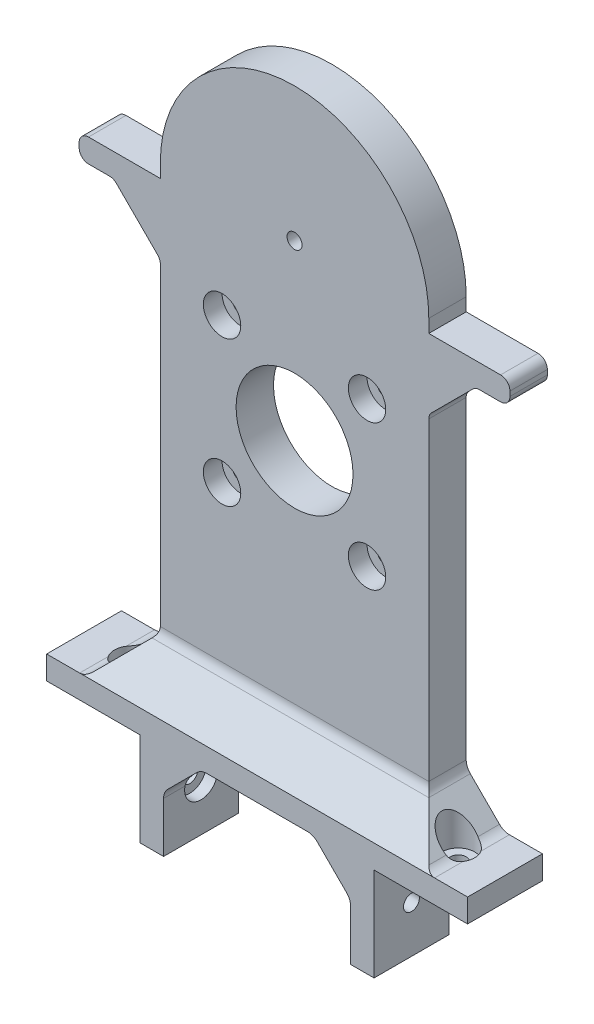
SolidWorks part; units mm, degrees
ref_plane "Plano frontal" through (0, 0, 0) normal (0, 0, 1) x (1, 0, 0)
ref_plane "Plano superior" through (0, 0, 0) normal (0, 1, 0) x (1, 0, 0)
ref_plane "Plano direito" through (0, 0, 0) normal (1, 0, 0) x (0, 0, -1)
sketch "Esboço1" plane through (0, 0, 0) normal (0, 0, 1) x (1, 0, 0)
  line L0 (-20, 0) -> (20, 0)
  line L1 (-20, 0) -> (-20, -20)
  line L2 (-20, -20) -> (-25, -20)
  line L3 (-25, -20) -> (-25, 0)
  line L4 (-25, 0) -> (-45, 0)
  line L5 (-45, 0) -> (-45, 5)
  line L6 (-45, 5) -> (-28.7, 5)
  line L7 (-28.7, 5) -> (-28.7, 100)
  line L8 (0, -20) -> (0, 100) construction
  line L9 (-28.7, 100) -> (28.7, 100) construction
  line L10 (28.7, 5) -> (28.7, 100)
  line L11 (45, 5) -> (28.7, 5)
  line L12 (45, 0) -> (45, 5)
  line L13 (25, 0) -> (45, 0)
  line L14 (25, -20) -> (25, 0)
  line L15 (20, -20) -> (25, -20)
  line L16 (20, 0) -> (20, -20)
  arc A1 (28.7, 100) -> (-28.7, 100) centre (0, 100) ccw
  point P2 (0, 0)
  dimension "D1" = 40
  dimension "D2" = 20
  dimension "D3" = 5
  dimension "D4" = 95
  dimension "D5" = 57.4
extrude "Ressalto-extrusão1" add sketch "Esboço1" along normal blind 8 contours L10 A1 L7 L6 L5 L4 L3 L2 L1 L0 L16 L15 L14 L13 L12 L11 region at (0, 58.2075, 0)
sketch "Esboço2" plane through (0, 0, 8) normal (0, 0, 1) x (1, 0, 0)
  line L26 (-20, -20) -> (-25, -20)
  line L27 (-25, -20) -> (-25, 0)
  line L28 (-25, 0) -> (-45, 0)
  line L29 (-45, 0) -> (-45, 5)
  line L32 (0, -55) -> (0, 55) construction
  line L34 (45, 5) -> (-45, 5)
  line L35 (45, 0) -> (45, 5)
  line L36 (25, 0) -> (45, 0)
  line L37 (25, -20) -> (25, 0)
  line L38 (20, -20) -> (25, -20)
  line L39 (-20, -20) -> (-20, 0)
  line L40 (-20, 0) -> (20, 0)
  line L41 (20, 0) -> (20, -20)
extrude "Ressalto-extrusão2" add sketch "Esboço2" along normal blind 8
chamfer "Chanfro1" distance 8 angle 45 5 edges at (28.7, 5, 4) (-28.7, 5, 4) (0, 5, 8) (20, 0, 8) (-20, 0, 8)
sketch "Esboço3" plane through (0, 0, 0) normal (0, 0, -1) x (-1, 0, 0)
  circle A0 centre (0, 100) radius 1.6
  circle A1 centre (0, 63) radius 12.5
  arc A8 (28.7, 100) -> (-28.7, 100) centre (0, 100) ccw construction
  dimension "D1" = 3.2
  dimension "D2" = 25
  dimension "D4" = 37
extrude "Corte-extrusão1" cut sketch "Esboço3" against normal through all
fillet "Filete1" radius 3 9 edges at (28.7, 13, 4) (36.7, 5, 8) (0, 13, 8) (-28.7, 13, 4) (-36.7, 5, 8) (20, -8, 8) (12, 0, 8) (-20, -8, 8) (-12, 0, 8)
sketch "Esboço9" plane through (0, 0, 0) normal (0, -1, 0) x (1, 0, 0)
  line L0 (35, 16) -> (35, 0) construction
  line L1 (25, 16) -> (45, 16) construction
  line L2 (25, 0) -> (45, 0) construction
  line L3 (0, -8.8) -> (0, 8.8) construction
  line L4 (-35, 16) -> (-35, 0) construction
sketch "Esboço10" plane through (25, 0, 0) normal (1, 0, 0) x (0, 0, -1)
  line L0 (-16, -10) -> (0, -10) construction
  line L1 (-16, -20) -> (-16, 0) construction
  line L2 (0, -20) -> (0, 0) construction
hole_wizard "Rebaixo para parafuso com cabeça panela de M32" positions "Esboço11" profile "Esboço12" counterbore size "M3" standard "ISO"
sketch "Esboço11" plane through (0, 5, 0) normal (0, 1, 0) x (1, 0, 0)
  line L0 (35, -16) -> (35, 0) construction
  line L1 (-35, -16) -> (-35, 0) construction
  point P0 (35, -8)
  point P4 (-35, -8)
sketch "Esboço12" plane through (35, 5, 8) normal (1, 0, 0) x (0, 0, 1)
  line L0 (0, 0) -> (0, 7.0215)
  line L1 (0, 7.0215) -> (1.7, 6)
  line L2 (1.7, 6) -> (1.7, 2.4)
  line L3 (1.7, 2.4) -> (3.5, 2.4)
  line L4 (3.5, 2.4) -> (3.5, 0)
  line L5 (3.5, 0) -> (0, 0)
  line L10 (0, 7.0215) -> (-1.7, 6) construction
  line L11 (0, -6.35) -> (0, 107.95) construction
  dimension "Hole Dia." = 3.4
  dimension "Hole Depth" = 6
  dimension "C'Bore Dia." = 7
  dimension "C'Bore Depth" = 2.4
  dimension "Drill Angle" = 118
sketch "Esboço13" plane through (0, 5, 0) normal (0, 1, 0) x (1, 0, 0)
  line L0 (-35, -16) -> (-35, 0) construction
  line L1 (0, -8.8) -> (0, 8.8) construction
  circle A0 centre (-35, -8) radius 3.5
  circle A1 centre (-35, -8) radius 3.5 construction
  circle A2 centre (35, -8) radius 3.5
extrude "Corte-extrusão3" cut sketch "Esboço13" along normal blind 10
hole_wizard "Rebaixo para parafuso com cabeça panela de M33" positions "Esboço14" profile "Esboço15" counterbore size "M3" standard "ISO"
sketch "Esboço14" plane through (20, 0, 0) normal (-1, 0, 0) x (0, 0, 1)
  line L0 (16, -10) -> (0, -10) construction
  point P0 (8, -10)
sketch "Esboço15" plane through (20, -10, 8) normal (0, 1, 0) x (0, 0, 1)
  line L0 (0, 0) -> (0, 7.0215)
  line L1 (0, 7.0215) -> (1.7, 6)
  line L2 (1.7, 6) -> (1.7, 2.4)
  line L3 (1.7, 2.4) -> (3.5, 2.4)
  line L4 (3.5, 2.4) -> (3.5, 0)
  line L5 (3.5, 0) -> (0, 0)
  line L10 (0, 7.0215) -> (-1.7, 6) construction
  line L11 (0, -6.35) -> (0, 107.95) construction
  dimension "Hole Dia." = 3.4
  dimension "Hole Depth" = 6
  dimension "C'Bore Dia." = 7
  dimension "C'Bore Depth" = 2.4
  dimension "Drill Angle" = 118
hole_wizard "Rebaixo para parafuso com cabeça panela de M34" positions "Esboço16" profile "Esboço17" counterbore size "M3" standard "ISO"
sketch "Esboço16" plane through (-20, 0, 0) normal (1, 0, 0) x (0, 0, -1)
  line L0 (-16, -10) -> (0, -10) construction
  point P0 (-8, -10)
sketch "Esboço17" plane through (-20, -10, 8) normal (0, 1, 0) x (0, 0, -1)
  line L0 (0, 0) -> (0, 7.0215)
  line L1 (0, 7.0215) -> (1.7, 6)
  line L2 (1.7, 6) -> (1.7, 2.4)
  line L3 (1.7, 2.4) -> (3.5, 2.4)
  line L4 (3.5, 2.4) -> (3.5, 0)
  line L5 (3.5, 0) -> (0, 0)
  line L10 (0, 7.0215) -> (-1.7, 6) construction
  line L11 (0, -6.35) -> (0, 107.95) construction
  dimension "Hole Dia." = 3.4
  dimension "Hole Depth" = 6
  dimension "C'Bore Dia." = 7
  dimension "C'Bore Depth" = 2.4
  dimension "Drill Angle" = 118
sketch "Esboço18" plane through (20, 0, 0) normal (-1, 0, 0) x (0, 0, 1)
  line L0 (16, -10) -> (0, -10) construction
  circle A0 centre (8, -10) radius 3.5
  circle A1 centre (8, -10) radius 3.5 construction
extrude "Corte-extrusão4" cut sketch "Esboço18" along normal blind 2
mirror "Espelhar1" about plane through (0, 0, 0) normal (1, 0, 0) of "Corte-extrusão4"
sketch "Esboço19" plane through (0, 0, 8) normal (0, 0, 1) x (1, 0, 0)
  circle A0 centre (15.5, 78.5) radius 1.8
  circle A1 centre (15.5, 47.5) radius 1.8
  circle A2 centre (-15.5, 47.5) radius 1.8
  circle A3 centre (-15.5, 78.5) radius 1.8
  circle A4 centre (0, 63) radius 12.5 construction
  point P12 (0, 63)
  dimension "D1" = 3.6
  dimension "D2" = 4
extrude "Corte-extrusão5" cut sketch "Esboço19" against normal through all
sketch "Esboço20" plane through (0, 0, 8) normal (0, 0, 1) x (1, 0, 0)
  circle A0 centre (15.5, 78.5) radius 4
  circle A1 centre (15.5, 47.5) radius 4
  circle A2 centre (-15.5, 47.5) radius 4
  circle A3 centre (-15.5, 78.5) radius 4
  circle A4 centre (0, 63) radius 12.5 construction
  point P12 (0, 63)
  dimension "D1" = 8
  dimension "D2" = 4
extrude "Corte-extrusão6" cut sketch "Esboço20" against normal blind 4
sketch "Esboço21" plane through (0, 0, 0) normal (0, 0, -1) x (-1, 0, 0)
  line L0 (-28.7, 14.2426) -> (-28.7, 100) construction
  line L1 (-28.7, 97.2) -> (-46.05, 97.2)
  line L2 (-28.7, 97.2) -> (-28.7, 92.2)
  line L3 (-28.7, 92.2) -> (-46.05, 92.2)
  line L4 (-46.05, 97.2) -> (-46.05, 92.2)
  line L5 (0, 8.8) -> (0, -8.8) construction
  line L6 (28.7, 92.2) -> (46.05, 92.2)
  line L7 (46.05, 97.2) -> (46.05, 92.2)
  line L8 (28.7, 97.2) -> (46.05, 97.2)
  line L9 (28.7, 97.2) -> (28.7, 92.2)
  arc A0 (28.7, 100) -> (-28.7, 100) centre (0, 100) ccw construction
  dimension "D1" = 17.35
  dimension "D2" = 31.5
  dimension "D3" = 5
extrude "Ressalto-extrusão3" add sketch "Esboço21" against normal up to surface (8 mm away) up to face at (-11.5, 78.5, 8)
fillet "Filete2" radius 2 4 edges at (46.05, 92.2, 4) (46.05, 97.2, 4) (-46.05, 92.2, 4) (-46.05, 97.2, 4)
chamfer "Chanfro2" distance 10 angle 45 2 edges at (28.7, 92.2, 4) (-28.7, 92.2, 4)
fillet "Filete3" radius 2 4 edges at (-38.7, 92.2, 4) (-28.7, 82.2, 4) (38.7, 92.2, 4) (28.7, 82.2, 4)
